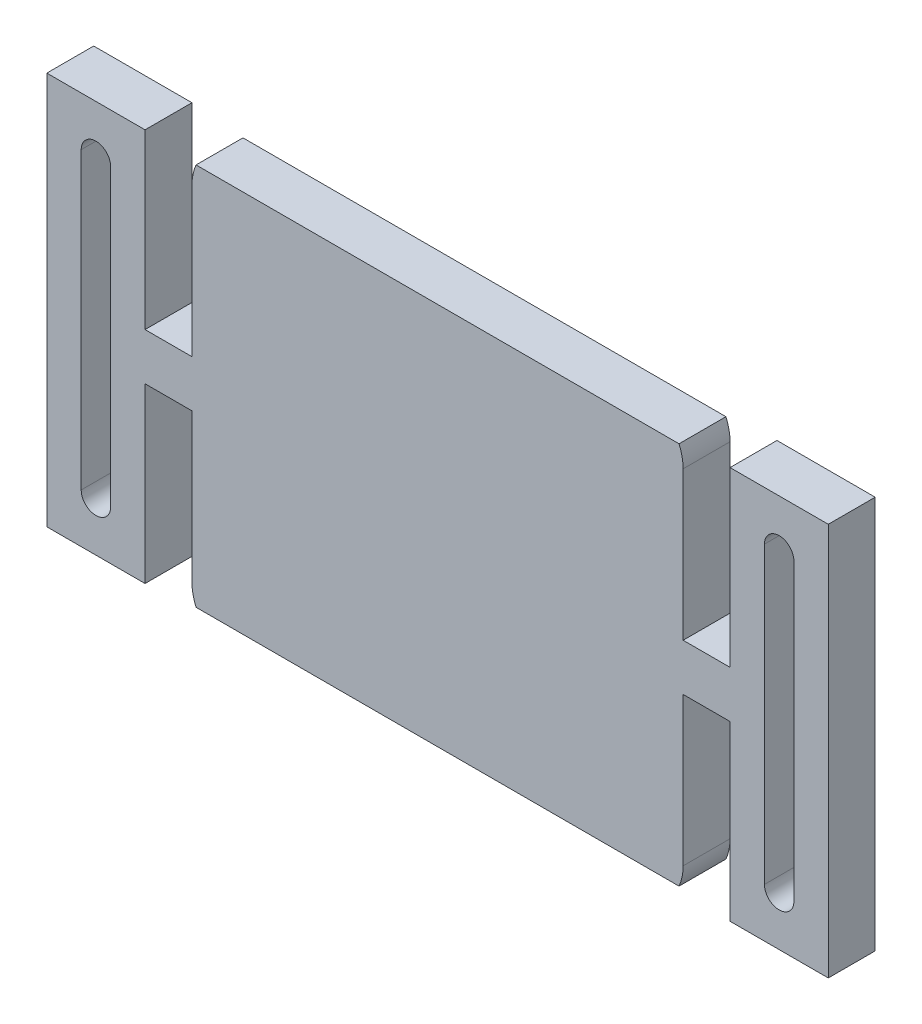
SolidWorks part; units mm, degrees
ref_plane "Front Plane" through (0, 0, 0) normal (0, 0, 1) x (1, 0, 0)
ref_plane "Top Plane" through (0, 0, 0) normal (0, 1, 0) x (1, 0, 0)
ref_plane "Right Plane" through (0, 0, 0) normal (1, 0, 0) x (0, 0, -1)
sketch "Sketch1" plane through (0, 0, 0) normal (0, 0, 1) x (1, 0, 0)
  line L0 (-4.7752, 24.8876) -> (0, 24.8876) construction
  line L1 (-4.7752, 20.1124) -> (-4.7752, 24.8876) construction
  line L2 (0, 20.1124) -> (0, 24.8876) construction
  line L3 (-4.7752, 20.1124) -> (0, 20.1124) construction
  line L4 (-4.7752, 24.8876) -> (0, 24.8876)
  line L5 (-4.7752, 20.1124) -> (-4.7752, 24.8876)
  line L6 (0, 20.1124) -> (0, 24.8876)
  line L7 (-4.7752, 20.1124) -> (0, 20.1124)
  line L8 (-59.5504, 24.8876) -> (-54.7752, 24.8876) construction
  line L9 (-59.5504, 20.1124) -> (-59.5504, 24.8876) construction
  line L10 (-54.7752, 20.1124) -> (-54.7752, 24.8876) construction
  line L11 (-59.5504, 20.1124) -> (-54.7752, 20.1124) construction
  line L12 (-59.5504, 24.8876) -> (-54.7752, 24.8876)
  line L13 (-59.5504, 20.1124) -> (-59.5504, 24.8876)
  line L14 (-54.7752, 20.1124) -> (-54.7752, 24.8876)
  line L15 (-59.5504, 20.1124) -> (-54.7752, 20.1124)
  line L16 (-9.7752, 45) -> (-49.7752, 45) construction
  line L17 (-54.7752, 5) -> (-54.7752, 40) construction
  line L18 (-9.7752, 0) -> (-49.7752, 0) construction
  line L19 (-4.7752, 40) -> (-4.7752, 5) construction
  line L20 (-9.7752, 45) -> (-49.7752, 45)
  line L21 (-54.7752, 5) -> (-54.7752, 40)
  line L22 (-9.7752, 0) -> (-49.7752, 0)
  line L23 (-4.7752, 40) -> (-4.7752, 5)
  line L24 (-54.7752, 22.5) -> (-59.5504, 22.5)
  line L25 (-59.5504, 24.8876) -> (-59.5504, 20.1124)
  line L27 (-59.5504, 2.5) -> (-59.5504, 42.5)
  line L30 (-59.5504, 42.5) -> (-64.5504, 42.5)
  line L32 (-64.5504, 2.5) -> (-59.5504, 2.5)
  line L33 (-66.0504, 37.5) -> (-66.0504, 7.5)
  line L34 (-63.0504, 37.5) -> (-63.0504, 7.5)
  line L35 (-64.5504, 2.5) -> (-69.5504, 2.5)
  line L36 (-69.5504, 2.5) -> (-69.5504, 42.5)
  line L37 (-69.5504, 42.5) -> (-64.5504, 42.5)
  line L38 (-29.7752, 45) -> (-29.7752, 0) construction
  line L39 (3.5, 37.5) -> (3.5, 7.5)
  line L40 (5, 2.5) -> (0, 2.5)
  line L41 (5, 2.5) -> (10, 2.5)
  line L42 (0, 2.5) -> (0, 42.5)
  line L43 (6.5, 37.5) -> (6.5, 7.5)
  line L44 (10, 2.5) -> (10, 42.5)
  line L45 (0, 42.5) -> (5, 42.5)
  line L46 (10, 42.5) -> (5, 42.5)
  line L47 (-9.7752, 45) -> (-9.7752, 42)
  line L48 (-9.7752, 42) -> (-54.3578, 42)
  line L49 (-9.7752, 42) -> (-5.1926, 42)
  line L50 (-54.7752, 22.5) -> (-4.7752, 22.5) construction
  line L51 (-9.7752, 3) -> (-5.1926, 3)
  line L52 (-9.7752, 3) -> (-54.3578, 3)
  line L53 (-54.3578, 42) -> (-54.3578, 45)
  line L54 (-54.3578, 45) -> (-5.1926, 45)
  line L55 (-5.1926, 45) -> (-5.1926, 42)
  line L56 (-54.3578, 3) -> (-54.3578, 0)
  line L57 (-54.3578, 0) -> (-5.1926, 0)
  line L58 (-5.1926, 0) -> (-5.1926, 3)
  arc A0 (-4.7752, 40) -> (-9.7752, 45) centre (-9.7752, 40) ccw construction
  arc A1 (-49.7752, 45) -> (-54.7752, 40) centre (-49.7752, 40) ccw construction
  arc A2 (-54.7752, 5) -> (-49.7752, 0) centre (-49.7752, 5) ccw construction
  arc A3 (-9.7752, 0) -> (-4.7752, 5) centre (-9.7752, 5) ccw construction
  arc A4 (-4.7752, 40) -> (-9.7752, 45) centre (-9.7752, 40) ccw
  arc A5 (-49.7752, 45) -> (-54.7752, 40) centre (-49.7752, 40) ccw
  arc A6 (-54.7752, 5) -> (-49.7752, 0) centre (-49.7752, 5) ccw
  arc A7 (-9.7752, 0) -> (-4.7752, 5) centre (-9.7752, 5) ccw
  circle A8 centre (-64.5504, 37.5) radius 1.5
  circle A9 centre (-64.5504, 7.5) radius 1.5
  circle A10 centre (5, 7.5) radius 1.5
  circle A11 centre (5, 37.5) radius 1.5
  point P28 (-62.0504, 42.5)
  point P58 (-29.7752, 22.5)
  dimension "D3" = 3
  dimension "D1" = 20
  dimension "D2" = 5
  dimension "D4" = 5
  dimension "D5" = 5
  dimension "D6" = 5
  dimension "D7" = 3
extrude "Boss-Extrude1" add sketch "Sketch1" along normal blind 4.7752 contours L22 A7 L23 L5 A4 L20 A5 L21 L14 A6 | L12 L14 L15 L13 | L4 L6 L7 L5 | L20 A5 L21 A6 L22 A7 L23 A4 | L40 L42 L45 L46 L44 L41 | L32 L27 L30 L37 L36 L35 region at (-29.7752, 22.5, 0)
extrude "Cut-Extrude1" cut sketch "Sketch1<3>" along normal through all contours L33 A9 L34 A8 | A8 | A9 | L43 A11 L39 A10 | A10 | A11 region at (-64.5504, 22.5, 0) region at (-64.5504, 37.5, 0) region at (-64.5504, 7.5, 0) region at (5, 22.5, 0) region at (5, 37.5, 0) region at (5, 7.5, 0)
sketch "Sketch1<3>" plane through (0, 0, 0) normal (0, 0, 1) x (1, 0, 0) same geometry as "Sketch1"
extrude "Cut-Extrude2" cut sketch "Sketch1<5>" along normal blind 10 contours L49 A4 L47 | L20 A5 L48 L47 | L22 A7 L51 L52 A6 region at (-7.9586, 43.2375, 0) region at (-29.7752, 1.5372, 0) region at (-31.4392, 43.48, 0)
sketch "Sketch1<5>" plane through (0, 0, 0) normal (0, 0, 1) x (1, 0, 0) same geometry as "Sketch1"
